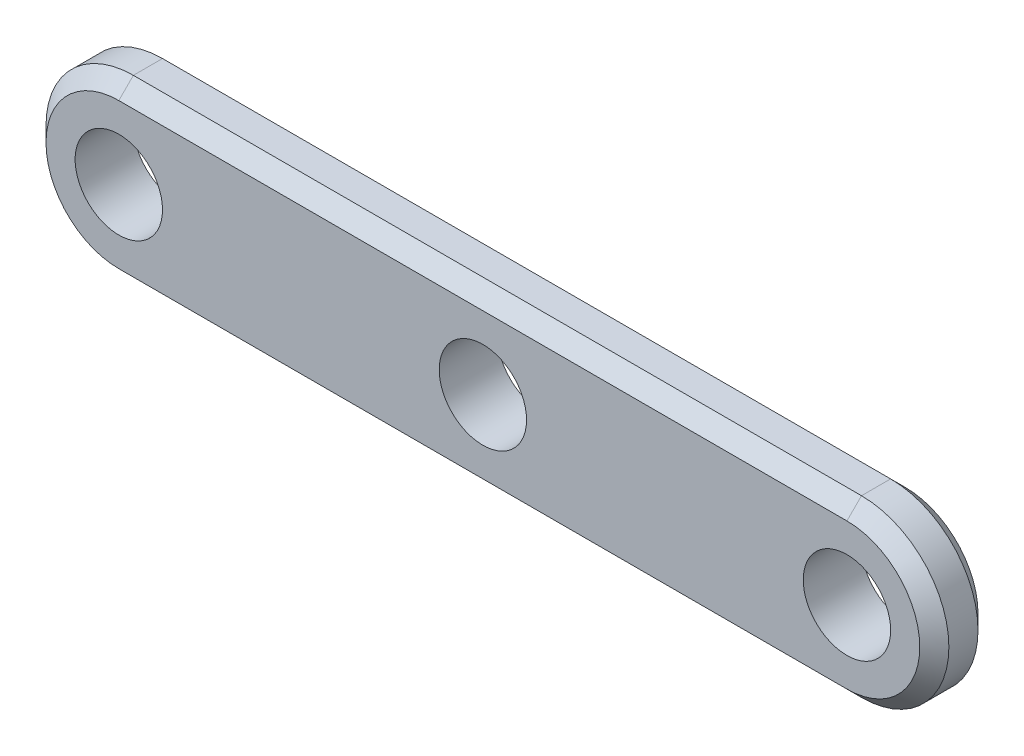
SolidWorks part; units mm, degrees
material "Copper"
ref_plane "Front Plane" through (0, 0, 0) normal (0, 0, 1) x (1, 0, 0)
ref_plane "Top Plane" through (0, 0, 0) normal (0, 1, 0) x (1, 0, 0)
ref_plane "Right Plane" through (0, 0, 0) normal (1, 0, 0) x (0, 0, -1)
sketch "Sketch1" plane through (0, 0, 0) normal (0, 0, 1) x (1, 0, 0)
  line L0 (0, 6) -> (50, 6)
  line L1 (50, -6) -> (0, -6)
  line L2 (0, 0) -> (50, 0) construction
  circle A0 centre (0, 0) radius 6
  circle A1 centre (50, 0) radius 6
  circle A2 centre (50, 0) radius 3
  circle A3 centre (0, 0) radius 3
  circle A4 centre (25, 0) radius 3
  dimension "D1" = 12
  dimension "D2" = 50
  dimension "D3" = 6
extrude "Boss-Extrude1" add sketch "Sketch1" along normal blind 4 contours A1 L0 A0 L1 | A1 A2 | A0 A3 | L2 A0 L1 A1 A4 region at (25, 3.2183, 0) region at (4.1226, 4.1226, 0) region at (54.1226, 4.1226, 0) region at (25, -3.2183, 0)
chamfer "Chamfer1" distance 1 angle 45 8 edges at (25, -6, 0) (-6, 0, 0) (56, 0, 0) (25, 6, 0) (25, -6, 4) (-6, 0, 4) (56, 0, 4) (25, 6, 4)
